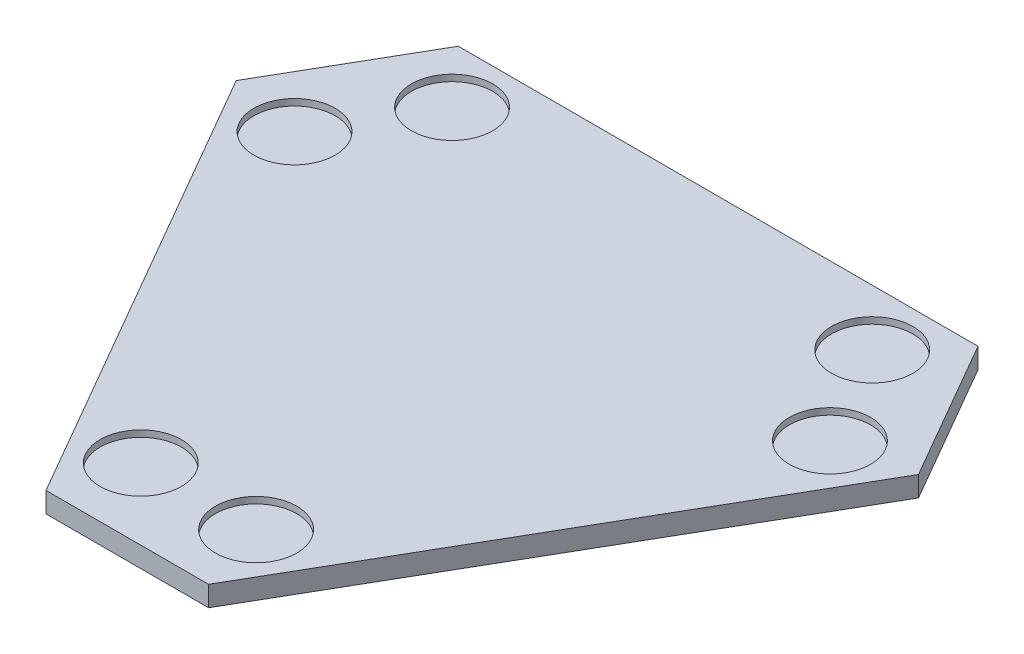
SolidWorks part; units mm, degrees
note: '?' marks a value the reader was unsure of. The reader was unsure of these and kept them because the rebuilt part matched: shared geometry of "Sketch1<5>".
ref_plane "Front Plane" through (0, 0, 0) normal (0, 0, 1) x (1, 0, 0)
ref_plane "Top Plane" through (0, 0, 0) normal (0, 1, 0) x (1, 0, 0)
ref_plane "Right Plane" through (0, 0, 0) normal (1, 0, 0) x (0, 0, -1)
sketch "Sketch1" plane through (0, 0, 0) normal (0, 1, 0) x (1, 0, 0)
  line L0 (103.923, 60) -> (0, -120)
  line L1 (0, -120) -> (-103.923, 60)
  line L2 (-103.923, 60) -> (103.923, 60)
  line L3 (103.923, 60) -> (-51.9615, -30) construction
  line L4 (-103.923, 60) -> (51.9615, -30) construction
  line L5 (-337.0463, -245.6128) -> (-234.4722, -67.9492)
  line L6 (-234.4722, -67.9492) -> (-131.898, -245.6128)
  line L7 (-131.898, -245.6128) -> (-337.0463, -245.6128)
  line L8 (-337.0463, -245.6128) -> (-183.1851, -156.781) construction
  line L9 (-131.898, -245.6128) -> (-285.7592, -156.781) construction
  line L10 (-147.8461, -85.359) -> (0, 170.718)
  line L11 (0, 170.718) -> (147.8461, -85.359)
  line L12 (147.8461, -85.359) -> (-147.8461, -85.359)
  line L13 (-147.8461, -85.359) -> (73.923, 42.6795) construction
  line L14 (147.8461, -85.359) -> (-73.923, 42.6795) construction
  line L15 (-30.1036, -67.859) -> (0, -67.859) construction
  line L16 (0, 60) -> (0, -120) construction
  line L18 (-88.2227, 32.8062) -> (0, 32.8062) construction
  circle A0 centre (0, 0) radius 60 construction
  circle A1 centre (-14.187, -67.859) radius 10
  circle A2 centre (14.187, -67.859) radius 10
  point P21 (20, -85.359)
  point P24 (-20, -85.359)
  point P25 (-27.2169, -69.4629)
  dimension "D1" = 120
  dimension "D3" = 20
  dimension "D2" = 40
  dimension "D4" = 17.5
extrude "Boss-Extrude1" add sketch "Sketch1" along normal blind 5 contours L12 L0 L11 L2 L10 L1
extrude "Cut-Extrude4" cut sketch "Sketch1<5>" against normal blind 1.6 from surface at 5 starting at face at (0, 5, 0)
sketch "Sketch1<5>" plane through (0, 0, 0) normal (0, 1, 0) x (1, 0, 0) same geometry as "Sketch1"
sketch "Sketch3" plane through (0, 0, 0) normal (0, 0, 1) x (1, 0, 0)
  line L0 (0, 0) -> (0, 22.4752) construction
pattern_circular "CirPattern1" count 3 over 360 about axis through (0, 0, 0) along (0, 1, 0) of "Cut-Extrude4"
ref_axis "Axis1" through (0, -134.7666, 0) along (0, 1, 0)?
